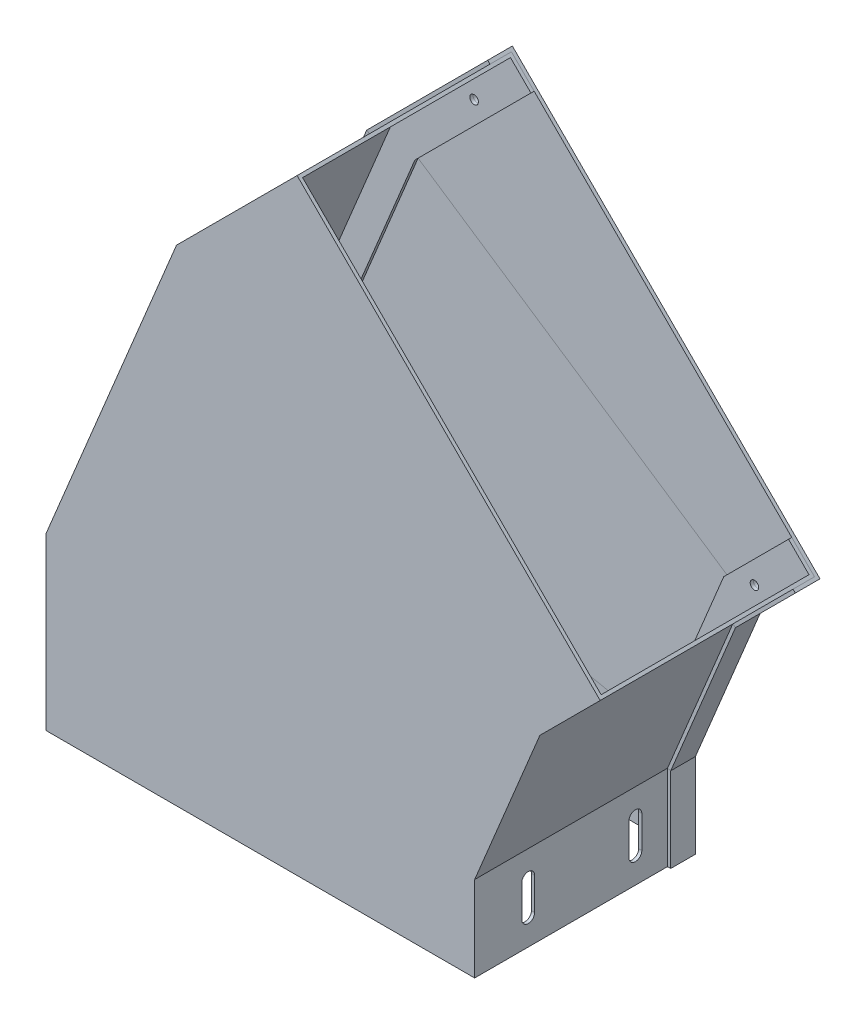
SolidWorks part; units mm, degrees
material "Plain Carbon Steel"
ref_plane "Front Plane" through (0, 0, 0) normal (0, 0, 1) x (1, 0, 0)
ref_plane "Top Plane" through (0, 0, 0) normal (0, 1, 0) x (1, 0, 0)
ref_plane "Right Plane" through (0, 0, 0) normal (1, 0, 0) x (0, 0, -1)
sketch "ElbowArc" plane through (0, 0, 0) normal (0, 0, 1) x (1, 0, 0)
  line L2 (-300, 0) -> (-300, 59.6737)
  line L3 (-300, 59.6737) -> (-254.3277, 169.9363)
  line L4 (-254.3277, 169.9363) -> (-212.132, 212.132)
  arc A0 (-300, 0) -> (-212.132, 212.132) centre (0, 0) cw construction
  dimension "BendRadius" = 300
  dimension "BendAngle" = 45
sketch "Sketch1" plane through (0, 0, 0) normal (0, 1, 0) x (1, 0, 0)
  line L0 (-300, 0) -> (203.1914, 0) construction
  line L1 (-200, -50) -> (-400, -50)
  line L2 (-400, -50) -> (-400, 50)
  line L3 (-200, -50) -> (-200, 50)
  line L4 (-398.5, -48.5) -> (-398.5, 48.5)
  line L5 (-201.5, -48.5) -> (-398.5, -48.5)
  line L6 (-201.5, -48.5) -> (-201.5, 48.5)
  line L7 (-400, 50) -> (-385, 50)
  line L8 (-385, 48.5) -> (-398.5, 48.5)
  line L9 (-200, 50) -> (-400, -50) construction
  line L10 (-385, 48.5) -> (-385, 50)
  line L11 (-200, 50) -> (-215, 50)
  line L12 (-398.5, -48.5) -> (-398.5, 50) construction
  line L13 (-215, 50) -> (-215, 48.5)
  line L14 (-215, 48.5) -> (-201.5, 48.5)
  line L16 (-201.5, -48.5) -> (-201.5, 50) construction
  dimension "D2" = 15
  dimension "Width" = 200
  dimension "AlignmentAngle" = 0
  dimension "Height" = 100
  dimension "D1" = 1.5
  dimension "Thickness" = 1.5
sweep "Sweep1" add profiles "Sketch1" path "ElbowArc"
ref_plane "Plane1" through (-300, 0, 0) normal (1, 0, 0) x (0, 1, 0)
sketch "Sketch2" plane through (-300, 0, 0) normal (1, 0, 0) x (0, 0, -1)
  line L0 (-50, 20) -> (0, 20) construction
  line L2 (0, 20) -> (50, 20) construction
  line L3 (0, 0) -> (0, 40) construction
  line L7 (-25, 12.5) -> (-25, 27.5) construction
  line L8 (-28, 12.5) -> (-28, 27.5)
  line L9 (-22, 12.5) -> (-22, 27.5)
  line L10 (25, 12.5) -> (25, 27.5) construction
  line L11 (22, 12.5) -> (22, 27.5)
  line L12 (28, 12.5) -> (28, 27.5)
  line L13 (0, 0) -> (0, 59.6737) construction
  arc A0 (-28, 12.5) -> (-22, 12.5) centre (-25, 12.5) ccw
  arc A1 (-22, 27.5) -> (-28, 27.5) centre (-25, 27.5) ccw
  arc A2 (22, 12.5) -> (28, 12.5) centre (25, 12.5) ccw
  arc A3 (28, 27.5) -> (22, 27.5) centre (25, 27.5) ccw
  point P10 (-25, 20)
  point P16 (25, 20)
  dimension "D1" = 3
  dimension "D2" = 15
  dimension "D3" = 40
  dimension "D5" = 50
extrude "Cut-Extrude1" cut sketch "Sketch2" against normal through all and the other way through all
ref_plane "Plane2" through (-212.132, 212.132, 0) normal (0.7071, -0.7071, 0) x (0.7071, 0.7071, 0)
sketch "Sketch3" plane through (-212.132, 212.132, 0) normal (-0.7071, 0.7071, 0) x (-0.7071, -0.7071, 0)
  line L0 (20, 0) -> (20, -50) construction
  line L4 (20, 0) -> (20, 50) construction
  line L6 (40, 0) -> (0, 0) construction
  line L7 (59.6737, 0) -> (0, 0) construction
  line L9 (12.5, 25) -> (27.5, 25) construction
  line L10 (12.5, 28) -> (27.5, 28)
  line L11 (12.5, 22) -> (27.5, 22)
  line L12 (12.5, -25) -> (27.5, -25) construction
  line L13 (12.5, -22) -> (27.5, -22)
  line L14 (12.5, -28) -> (27.5, -28)
  arc A0 (12.5, 28) -> (12.5, 22) centre (12.5, 25) ccw
  arc A1 (27.5, 22) -> (27.5, 28) centre (27.5, 25) ccw
  arc A2 (12.5, -22) -> (12.5, -28) centre (12.5, -25) ccw
  arc A3 (27.5, -28) -> (27.5, -22) centre (27.5, -25) ccw
  point P12 (20, 25)
  point P18 (20, -25)
  dimension "D1" = 3
  dimension "D2" = 15
  dimension "D3" = 40
  dimension "D5" = 50
extrude "Cut-Extrude2" cut sketch "Sketch3" against normal through all and the other way through all
ref_plane "Plane3" through (0, 0, 0) normal (0, 0, 1) x (0, 1, 0)
sketch "Sketch4" plane through (0, 0, 0) normal (0, 0, -1) x (-1, 0, 0)
  line L0 (200, 30) -> (400, 30) construction
  line L1 (300, 0) -> (300, 59.6737) construction
  circle A0 centre (392.5, 30) radius 2
  circle A1 centre (207.5, 30) radius 2
  point P6 (300, 30)
  dimension "D4" = 4
  dimension "D1" = 200
  dimension "D2" = 7.5
  dimension "D3" = 7.5
  dimension "D5" = 30
extrude "Cut-Extrude3" cut sketch "Sketch4" along normal through all
ref_plane "Plane4" through (0, 0, 0) normal (0, 0, 1) x (0.7071, 0.7071, 0)
sketch "Sketch5" plane through (0, 0, 0) normal (0, 0, 1) x (0.7071, 0.7071, 0)
  line L0 (-30, 400) -> (-30, 200) construction
  line L1 (-59.6737, 300) -> (0, 300) construction
  circle A0 centre (-30, 392.5) radius 2
  circle A1 centre (-30, 207.5) radius 2
  point P6 (-30, 300)
  dimension "D2" = 4
  dimension "D1" = 30
  dimension "D3" = 200
  dimension "D4" = 7.5
  dimension "D5" = 7.5
extrude "Cut-Extrude4" cut sketch "Sketch5" against normal up to next
sketch "Sketch8" plane through (0, 0, 0) normal (0, 1, 0) x (1, 0, 0)
  line L0 (-400, 40) -> (-400, 50)
  line L1 (-400, 50) -> (-200, 50)
  line L2 (-200, 50) -> (-200, 40)
  line L3 (-125.9212, 0) -> (-300, 0) construction
  line L4 (-300, 0) -> (203.1914, 0) construction
  line L5 (-401.5, 40) -> (-401.5, 51.5)
  line L6 (-401.5, 51.5) -> (-198.5, 51.5)
  line L7 (-198.5, 51.5) -> (-198.5, 40)
  line L8 (-198.5, 40) -> (-200, 40)
  line L9 (-400, 40) -> (-401.5, 40)
  line L10 (-300, 50) -> (-300, -50) construction
  line L11 (-201.5, -48.5) -> (-398.5, -48.5) construction
  point P8 (-300, 0)
  dimension "Thickness" = 1.5
  dimension "D2" = 200
  dimension "D3" = 10
  dimension "D1" = 100
sweep "Sweep2" add profiles "Sketch8" path "ElbowArc<2>"
sketch "ElbowArc<2>" plane through (0, 0, 0) normal (0, 0, 1) x (1, 0, 0) same geometry as "ElbowArc"
sketch "Sketch10" plane through (0, 0, 0) normal (0, 0, 1) x (0, 1, 0)
  circle A2 centre (30, 207.5) radius 2 construction
  circle A3 centre (30, 392.5) radius 2 construction
  circle A4 centre (30, 207.5) radius 2
  circle A5 centre (30, 392.5) radius 2
extrude "Cut-Extrude5" cut sketch "Sketch10" against normal through all
sketch "Sketch11" plane through (0, 0, 0) normal (0, 0, 1) x (0.7071, 0.7071, 0)
  circle A2 centre (-30, 207.5) radius 2 construction
  circle A3 centre (-30, 392.5) radius 2 construction
  circle A4 centre (-30, 207.5) radius 2
  circle A5 centre (-30, 392.5) radius 2
extrude "Cut-Extrude6" cut sketch "Sketch11" against normal through all
sketch "Sketch6" plane through (0, 0, 0) normal (0, 0, -1) x (-1, 0, 0)
  point P0 (300, 0)
  point P1 (212.132, 212.132)
other "CPoint1" parameters "Diameter"=10, "StubLength"=200
ref_axis "Axis2" through (-205.061, 219.2031, 0) along (-0.7071, -0.7071, 0)
other "CPoint2" parameters "Diameter"=10, "StubLength"=200
ref_axis "Axis3" through (-300, -10, 0) along (0, 1, 0)
equation "\"D5@Sketch3\"=\"Height@Sketch1\"/2"
equation "\"D5@Sketch2\"=\"Height@Sketch1\"/2"
equation "\"D1@Plane1\"=\"AlignmentAngle@Sketch1\""
equation "\"D1@Sketch1\"=\"Thickness@Sketch1\""
equation "\"D1@Sketch4\" = \"Width@Sketch1\""
equation "\"D1@Plane3\"=\"AlignmentAngle@Sketch1\""
equation "\"D1@Plane4\"=\"AlignmentAngle@Sketch1\""
equation "\"D3@Sketch5\" = \"Width@Sketch1\""
equation "\"D4@Sketch5\" = \"D2@Sketch1\" / 2"
equation "\"D5@Sketch5\" = \"D4@Sketch5\""
equation "\"D2@Sketch4\" = \"D2@Sketch1\" / 2"
equation "\"D3@Sketch4\" = \"D2@Sketch4\""
equation "\"D1@Sketch8\"=\"Height@Sketch1\""
equation "\"D2@Sketch8\"=\"Width@Sketch1\""
equation "\"Thickness@Sketch8\" = \"Thickness@Sketch1\""
